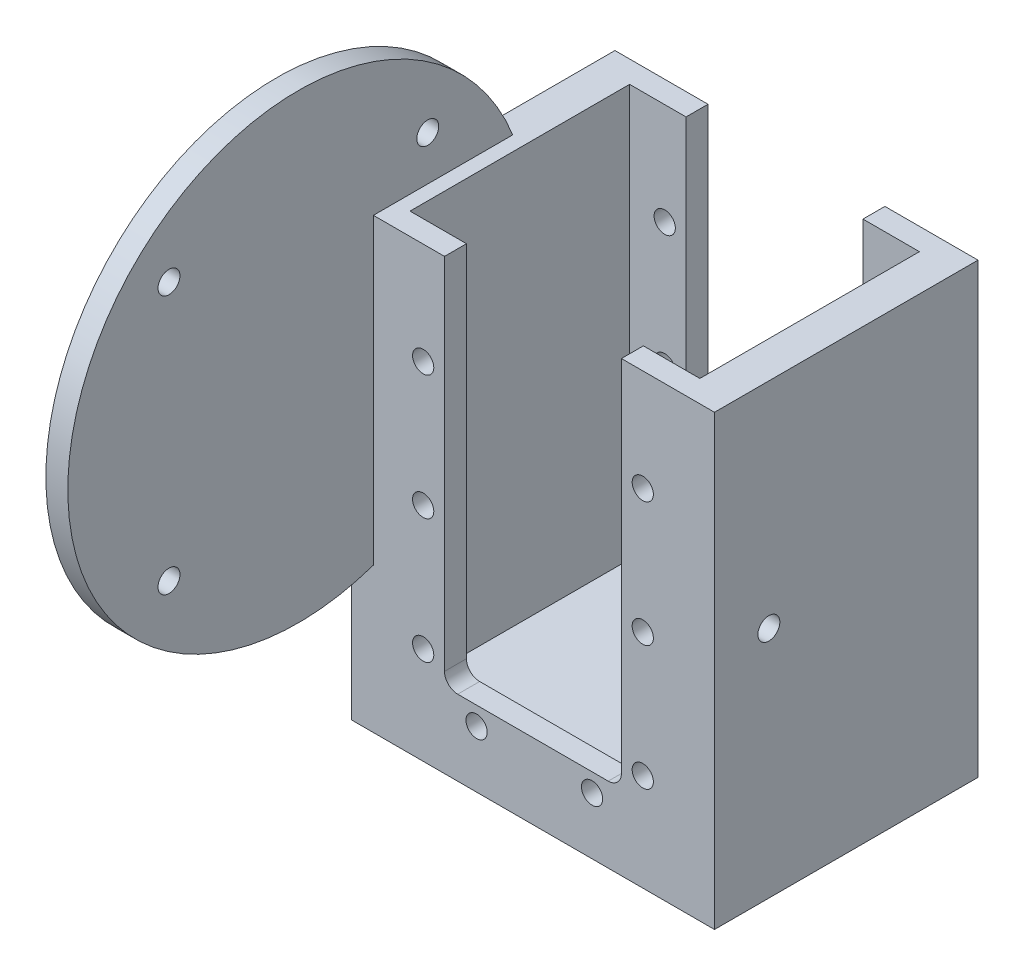
SolidWorks part; units mm, degrees
material "ABS"
ref_plane "Front Plane" through (0, 0, 0) normal (0, 0, 1) x (1, 0, 0)
ref_plane "Top Plane" through (0, 0, 0) normal (0, 1, 0) x (1, 0, 0)
ref_plane "Right Plane" through (0, 0, 0) normal (1, 0, 0) x (0, 0, -1)
sketch "Sketch1" plane through (0, 0, 0) normal (0, 0, 1) x (1, 0, 0)
  line L0 (-10.285, 45) -> (-11.785, 45)
  line L1 (-12.4921, 44.7071) -> (-17.5063, 39.6929)
  line L2 (-17.7992, 38.9858) -> (-17.7992, 0.4142)
  line L3 (-17.5063, -0.2929) -> (-12.4921, -5.3071)
  line L4 (-11.785, -5.6) -> (11.7866, -5.6)
  line L5 (12.4937, -5.3071) -> (17.5079, -0.2929)
  line L6 (17.8008, 0.4142) -> (17.8008, 38.9858)
  line L7 (17.5079, 39.6929) -> (12.4937, 44.7071)
  line L8 (11.7866, 45) -> (10.285, 45)
  line L9 (11.785, 43.5) -> (11.785, 1.5)
  line L10 (10.285, 0) -> (-10.285, 0)
  line L11 (-11.785, 1.5) -> (-11.785, 43.5)
  line L12 (-10.285, 45) -> (10.285, 45)
  line L13 (24.8008, 56.1927) -> (24.8008, -14.4857)
  line L14 (-24.7992, 61.4878) -> (-24.7992, -15.9821)
  line L15 (-24.7992, 50.6) -> (24.8008, 50.6)
  line L16 (-11.785, -5.6) -> (-24.7992, -5.6)
  line L17 (11.7866, -5.6) -> (24.8008, -5.6)
  line L18 (-12.085, 1.5) -> (-12.085, 43.5)
  line L19 (10.285, -0.3) -> (-10.285, -0.3)
  line L20 (12.085, 43.5) -> (12.085, 1.5)
  line L21 (-10.285, 45.3) -> (10.285, 45.3)
  circle A0 centre (-14.9992, 36.7) radius 1.35
  circle A1 centre (-14.9992, 19.7) radius 1.35
  circle A2 centre (-14.9992, 2.7) radius 1.35
  circle A3 centre (-7.6975, -2.8) radius 1.35
  arc A4 (-10.285, 45) -> (-11.785, 43.5) centre (-10.285, 43.5) ccw
  arc A5 (-11.785, 45) -> (-12.4921, 44.7071) centre (-11.785, 44) ccw
  arc A6 (-17.5063, 39.6929) -> (-17.7992, 38.9858) centre (-16.7992, 38.9858) ccw
  arc A7 (-17.7992, 0.4142) -> (-17.5063, -0.2929) centre (-16.7992, 0.4142) ccw
  arc A8 (-12.4921, -5.3071) -> (-11.785, -5.6) centre (-11.785, -4.6) ccw
  arc A9 (11.7866, -5.6) -> (12.4937, -5.3071) centre (11.7866, -4.6) ccw
  arc A10 (17.5079, -0.2929) -> (17.8008, 0.4142) centre (16.8008, 0.4142) ccw
  arc A11 (17.8008, 38.9858) -> (17.5079, 39.6929) centre (16.8008, 38.9858) ccw
  arc A12 (12.4937, 44.7071) -> (11.7866, 45) centre (11.7866, 44) ccw
  arc A13 (11.785, 43.5) -> (10.285, 45) centre (10.285, 43.5) ccw
  arc A14 (10.285, 0) -> (11.785, 1.5) centre (10.285, 1.5) ccw
  arc A15 (-11.785, 1.5) -> (-10.285, 0) centre (-10.285, 1.5) ccw
  circle A16 centre (8.0763, -2.8) radius 1.35
  circle A17 centre (15.0008, 2.7) radius 1.35
  circle A18 centre (15.0008, 19.7) radius 1.35
  circle A19 centre (15.0008, 36.7) radius 1.35
  circle A20 centre (-14.9992, 36.7) radius 1.45
  circle A21 centre (-14.9992, 19.7) radius 1.45
  circle A22 centre (-14.9992, 2.7) radius 1.45
  circle A23 centre (-7.6975, -2.8) radius 1.45
  circle A24 centre (8.0763, -2.8) radius 1.45
  circle A25 centre (15.0008, 2.7) radius 1.45
  circle A26 centre (15.0008, 19.7) radius 1.45
  circle A27 centre (15.0008, 36.7) radius 1.45
  arc A28 (-10.285, 45.3) -> (-12.085, 43.5) centre (-10.285, 43.5) ccw
  arc A29 (-12.085, 1.5) -> (-10.285, -0.3) centre (-10.285, 1.5) ccw
  arc A30 (10.285, -0.3) -> (12.085, 1.5) centre (10.285, 1.5) ccw
  arc A31 (12.085, 43.5) -> (10.285, 45.3) centre (10.285, 43.5) ccw
  dimension "D2" = 7
  dimension "D3" = 7
  dimension "D4" = 5.6
  dimension "D5" = 0.3
  dimension "D1" = 0.1
extrude "Boss-Extrude1" add sketch "Sketch1" along normal blind 3 contours A31 L8 A12 L7 A11 L6 A10 L5 A9 L17 L13 L15 L14 L16 A8 L3 A7 L2 A6 L1 A5 L0 A28 L21 | A31 L20 A30 L19 A29 L18 A28 L0 A5 L1 A6 L2 A7 L3 A8 L4 A9 L5 A10 L6 A11 L7 A12 L8 A27 A26 A25 A24 A23 A22 A21 A20 region at (-12.4162, 44.6437, 0) region at (-11.5325, 45.7496, 0)
extrude "Boss-Extrude2" add sketch "Sketch1<3>" against normal blind 3 from offset 30 separate body contours A31 L8 A12 L7 A11 L6 A10 L5 A9 L17 L13 L15 L14 L16 A8 L3 A7 L2 A6 L1 A5 L0 A28 L21 | A31 L20 A30 L19 A29 L18 A28 L0 A5 L1 A6 L2 A7 L3 A8 L4 A9 L5 A10 L6 A11 L7 A12 L8 A27 A26 A25 A24 A23 A22 A21 A20 region at (-12.4162, 44.6437, 0) region at (-11.5325, 45.7496, 0) offset against normal yes
sketch "Sketch1<3>" plane through (0, 0, 0) normal (0, 0, 1) x (1, 0, 0) same geometry as "Sketch1"
sketch "Sketch2" plane through (0, 0, 3) normal (0, 0, 1) x (1, 0, 0)
  line L0 (-12.085, 43.5) -> (-12.085, 56.6919)
  line L1 (-12.085, 56.6919) -> (12.085, 56.6919)
  line L2 (12.085, 56.6919) -> (12.085, 43.5)
  line L3 (-12.085, 43.5) -> (12.085, 43.5)
extrude "Cut-Extrude1" cut sketch "Sketch2" against normal through all
sketch "Sketch3" plane through (0, 0, -33) normal (0, 0, -1) x (-1, 0, 0)
  line L0 (-19.8008, 50.6) -> (-19.8008, -5.6)
  line L1 (-12.085, 50.6) -> (-24.8008, 50.6) construction
  line L2 (24.7992, -5.6) -> (-24.8008, -5.6) construction
  line L3 (-24.8008, 50.6) -> (-24.8008, -5.6) construction
  line L4 (19.7992, 50.6) -> (19.7992, -5.6)
  line L5 (24.7992, 50.6) -> (12.085, 50.6) construction
  line L6 (24.7992, 50.6) -> (24.7992, -5.6) construction
  line L15 (24.7992, 50.6) -> (12.085, 50.6)
  line L16 (12.085, 50.6) -> (12.085, 1.5)
  line L17 (10.285, -0.3) -> (-10.285, -0.3)
  line L18 (-12.085, 1.5) -> (-12.085, 50.6)
  line L19 (-12.085, 50.6) -> (-24.8008, 50.6)
  line L20 (-24.8008, 50.6) -> (-24.8008, -5.6)
  line L21 (-24.8008, -5.6) -> (24.7992, -5.6)
  line L22 (24.7992, -5.6) -> (24.7992, 50.6)
  line L23 (24.7992, 50.6) -> (12.085, 50.6)
  line L24 (12.085, 50.6) -> (12.085, 1.5)
  line L25 (10.285, -0.3) -> (-10.285, -0.3)
  line L26 (-12.085, 1.5) -> (-12.085, 50.6)
  line L27 (-12.085, 50.6) -> (-24.8008, 50.6)
  line L28 (-24.8008, 50.6) -> (-24.8008, -5.6)
  line L29 (-24.8008, -5.6) -> (24.7992, -5.6)
  line L30 (24.7992, -5.6) -> (24.7992, 50.6)
  arc A2 (10.285, -0.3) -> (12.085, 1.5) centre (10.285, 1.5) ccw
  arc A3 (-12.085, 1.5) -> (-10.285, -0.3) centre (-10.285, 1.5) ccw
  arc A4 (10.285, -0.3) -> (12.085, 1.5) centre (10.285, 1.5) ccw
  arc A5 (-12.085, 1.5) -> (-10.285, -0.3) centre (-10.285, 1.5) ccw
  line M13 (24.7992, 50.6) -> (12.085, 50.6)
  line M19 (-12.085, 50.6) -> (-24.8008, 50.6)
  line M20 (-24.8008, 50.6) -> (-24.8008, -5.6)
  line M21 (-24.8008, -5.6) -> (24.7992, -5.6)
  line M22 (24.7992, -5.6) -> (24.7992, 50.6)
  dimension "D1" = 5
  dimension "D2" = 5
  dimension "D3" = 0
extrude "Boss-Extrude3" add sketch "Sketch3" against normal up to surface (33 mm away) contours L0 M19 M20 M21 | L4 M13 M21 M22 region at (22.3008, 22.5, -33) region at (-22.2992, 22.5, -33) up to face at (0.0003, 19.2854, 0)
sketch "Sketch4" plane through (0, 0, -33) normal (0, 0, -1) x (-1, 0, 0)
  line L0 (-24.8008, -5.6) -> (-24.8008, -10.6)
  line L1 (-24.8008, -10.6) -> (24.7992, -10.6)
  line L2 (24.7992, -10.6) -> (24.7992, -5.6)
  line L3 (-24.8008, -5.6) -> (24.7992, -5.6) construction
  line L4 (-24.8008, -5.6) -> (24.7992, -5.6)
  dimension "D1" = 5
extrude "Boss-Extrude4" add sketch "Sketch4" against normal up to surface (36 mm away) up to face at (0.0003, 19.2854, 3)
sketch "Sketch6" plane through (-24.7992, 0, 0) normal (-1, 0, 0) x (0, 0, 1)
  circle A0 centre (13.25, 39) radius 31.5
  dimension "D3" = 63
  dimension "D1" = 11.6
  dimension "D2" = 10.25
extrude "Boss-Extrude6" add sketch "Sketch6" against normal blind 3
hole_wizard "Ø6.0mm Clearance Dowel Hole1" positions "Sketch7" profile "Sketch8" hole size "Ø6.0" standard "ISO" end condition through all
sketch "Sketch7" plane through (-24.7992, 0, 0) normal (-1, 0, 0) x (0, 0, 1)
  line L0 (13.25, 39) -> (-16.6201, 68.8701)
  line L2 (13.25, 39) -> (13.25, 84.7316)
  line L4 (13.25, 39) -> (38.4679, 13.7821)
  line L6 (13.25, 39) -> (-19.6868, 6.0632)
  line L8 (13.25, 39) -> (49.2698, 75.0198)
  circle A0 centre (13.25, 39) radius 25
  point P29 (-4.4277, 21.3223)
  point P31 (-4.4277, 56.6777)
  point P33 (30.9277, 56.6777)
  point P35 (30.9277, 21.3223)
  dimension "D1" = 50
  dimension "D2" = 45
sketch "Sketch8" plane through (-24.7992, 21.3223, 30.9277) normal (0, 1, 0) x (0, 0, 1)
  line L0 (0, 0) -> (0, 49.6)
  line L1 (0, 49.6) -> (1.5, 49.6)
  line L2 (1.5, 49.6) -> (1.5, 0)
  line L5 (1.5, 0) -> (0, 0)
  line L11 (0, -6.35) -> (0, 107.95) construction
  dimension "Thru Hole Dia." = 3
  dimension "Thru Hole Depth" = 49.6
